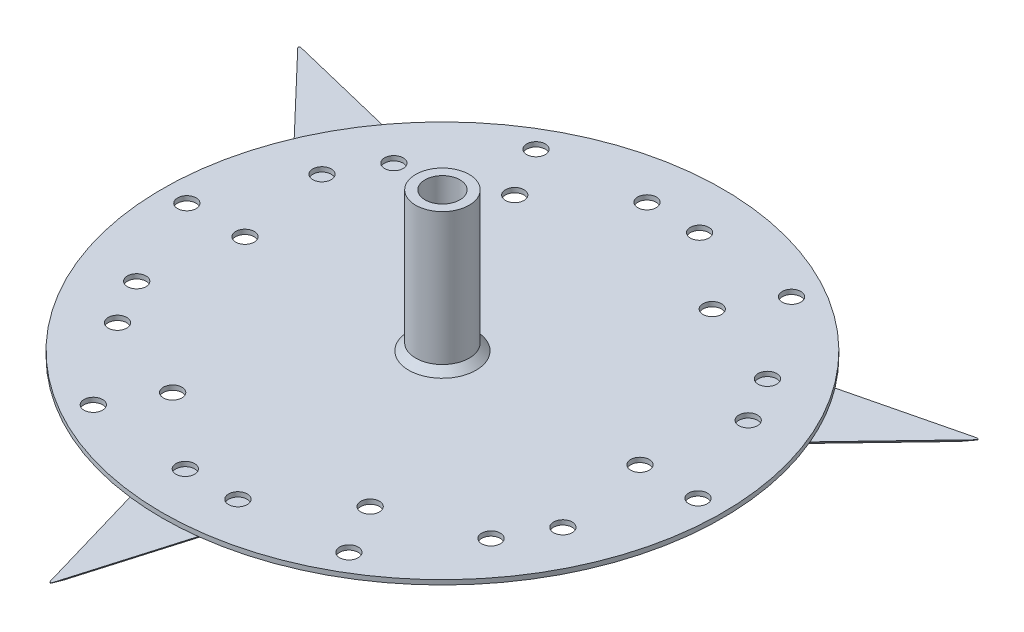
SolidWorks part; units mm, degrees
ref_plane "Front Plane" through (0, 0, 0) normal (0, 0, 1) x (1, 0, 0)
ref_plane "Top Plane" through (0, 0, 0) normal (0, 1, 0) x (1, 0, 0)
ref_plane "Right Plane" through (0, 0, 0) normal (1, 0, 0) x (0, 0, -1)
sketch "Sketch1" plane through (0, 0, 0) normal (0, 1, 0) x (1, 0, 0)
  line L0 (0, 0) -> (-11.3203, 99.3572) construction
  line L1 (0, 0) -> (11.3203, 99.3572) construction
  line L2 (0, 0) -> (0, 147.5667) construction
  circle A0 centre (0, 0) radius 120.65
  circle A1 centre (0, 0) radius 7.5
  circle A2 centre (0, 0) radius 85 construction
  circle A3 centre (-85, 0) radius 4
  circle A4 centre (-42.5, 73.6122) radius 4
  circle A5 centre (42.5, 73.6122) radius 4
  circle A6 centre (85, 0) radius 4
  circle A7 centre (42.5, -73.6122) radius 4
  circle A8 centre (-42.5, -73.6122) radius 4
  circle A9 centre (0, 0) radius 110 construction
  circle A10 centre (-110, 0) radius 4
  circle A11 centre (-55, 95.2628) radius 4
  circle A12 centre (55, 95.2628) radius 4
  circle A13 centre (110, 0) radius 4
  circle A14 centre (55, -95.2628) radius 4
  circle A15 centre (-55, -95.2628) radius 4
  circle A16 centre (0, 0) radius 100 construction
  circle A17 centre (-11.3203, 99.3572) radius 4
  circle A18 centre (11.3203, 99.3572) radius 4
  circle A19 centre (91.706, 39.8749) radius 4
  circle A20 centre (80.3857, 59.4823) radius 4
  circle A21 centre (80.3857, -59.4823) radius 4
  circle A22 centre (91.706, -39.8749) radius 4
  circle A23 centre (-11.3203, -99.3572) radius 4
  circle A24 centre (11.3203, -99.3572) radius 4
  circle A25 centre (-91.706, -39.8749) radius 4
  circle A26 centre (-80.3857, -59.4823) radius 4
  circle A27 centre (-80.3857, 59.4823) radius 4
  circle A28 centre (-91.706, 39.8749) radius 4
  point P19 (0, 0)
  point P33 (0, 0)
  point P61 (0, 0)
  dimension "D1" = 241.3
  dimension "D2" = 15
  dimension "D3" = 170
  dimension "D4" = 8
  dimension "D6" = 220
  dimension "D7" = 8
  dimension "D9" = 200
  dimension "D11" = 8
  dimension "D12" = 8
  dimension "D10" = 13
  dimension "D13" = 6.5
  dimension "D5" = 6
  dimension "D8" = 6
  dimension "D14" = 6
extrude "Boss-Extrude1" add sketch "Sketch1" along normal blind 2
sketch "Sketch2" plane through (0, 2, 0) normal (0, 1, 0) x (1, 0, 0)
  circle A0 centre (0, 0) radius 11.5
  circle A1 centre (0, 0) radius 7.5 construction
  circle A2 centre (0, 0) radius 7.5
  dimension "D1" = 23
extrude "Boss-Extrude2" add sketch "Sketch2" along normal blind 60
sketch "Sketch3" plane through (0, 0, 0) normal (0, 0, 1) x (1, 0, 0)
  line L0 (0, 0) -> (0, -18.5481) construction
  line L2 (0, 0) -> (15, 0)
  line L3 (0, -7.5) -> (9.6825, -7.5)
  line L4 (0, -7.5) -> (0, 0)
  arc A0 (14.5237, -3.75) -> (15, 0) centre (0, 0) ccw
  arc A1 (9.6825, -7.5) -> (14.5237, -3.75) centre (9.6825, -2.5) ccw
  dimension "D1" = 30
  dimension "D3" = 5
  dimension "D2" = 7.5
revolve "Revolve1" add sketch "Sketch3" angle 360 about L0
sketch "Sketch4" plane through (0, 0, 0) normal (0, -1, 0) x (1, 0, 0)
  line L0 (-19, 90) -> (19, 90)
  line L1 (19, 90) -> (19, 105)
  line L2 (-19, 90) -> (-19, 105)
  line L3 (-19, 105) -> (-0.4799, 168.3582)
  line L4 (19, 105) -> (0.4799, 168.3582)
  line L5 (0, 0) -> (0, 170) construction
  line L6 (0, 0) -> (147.2243, -85) construction
  line L7 (81.4327, -68.9545) -> (145.5625, -84.5947)
  line L8 (100.4327, -36.0455) -> (146.0424, -83.7635)
  line L9 (87.4423, -28.5455) -> (100.4327, -36.0455)
  line L10 (87.4423, -28.5455) -> (68.4423, -61.4545)
  line L11 (68.4423, -61.4545) -> (81.4327, -68.9545)
  line L12 (0, 0) -> (-147.2243, -85) construction
  line L13 (-100.4327, -36.0455) -> (-146.0424, -83.7635)
  line L14 (-81.4327, -68.9545) -> (-145.5625, -84.5947)
  line L15 (-68.4423, -61.4545) -> (-81.4327, -68.9545)
  line L16 (-68.4423, -61.4545) -> (-87.4423, -28.5455)
  line L17 (-87.4423, -28.5455) -> (-100.4327, -36.0455)
  arc A0 (-0.4799, 168.3582) -> (0.4799, 168.3582) centre (0, 168.2179) cw
  arc A1 (146.0424, -83.7635) -> (145.5625, -84.5947) centre (145.681, -84.1089) cw
  arc A2 (-145.5625, -84.5947) -> (-146.0424, -83.7635) centre (-145.681, -84.1089) cw
  point P9 (0, 90)
  point P30 (0, 0)
  dimension "D7" = 0.5
  dimension "D1" = 15
  dimension "D2" = 15
  dimension "D3" = 90
  dimension "D4" = 80
  dimension "D5" = 38
  dimension "D6" = 38
  dimension "D8" = 3
extrude "Boss-Extrude3" add sketch "Sketch4" along normal blind 2
chamfer "Chamfer1" distance 3 angle 45 1 edges at (0, 2, 11.5)
chamfer "Chamfer8" distance 2 angle 45 6 edges at (-123.2375, -2, -59.9045) (-113.4976, -2, -76.7746) (-9.74, -2, 136.6791) (9.74, -2, 136.6791) (123.2375, -2, -59.9045) (113.4976, -2, -76.7746)
